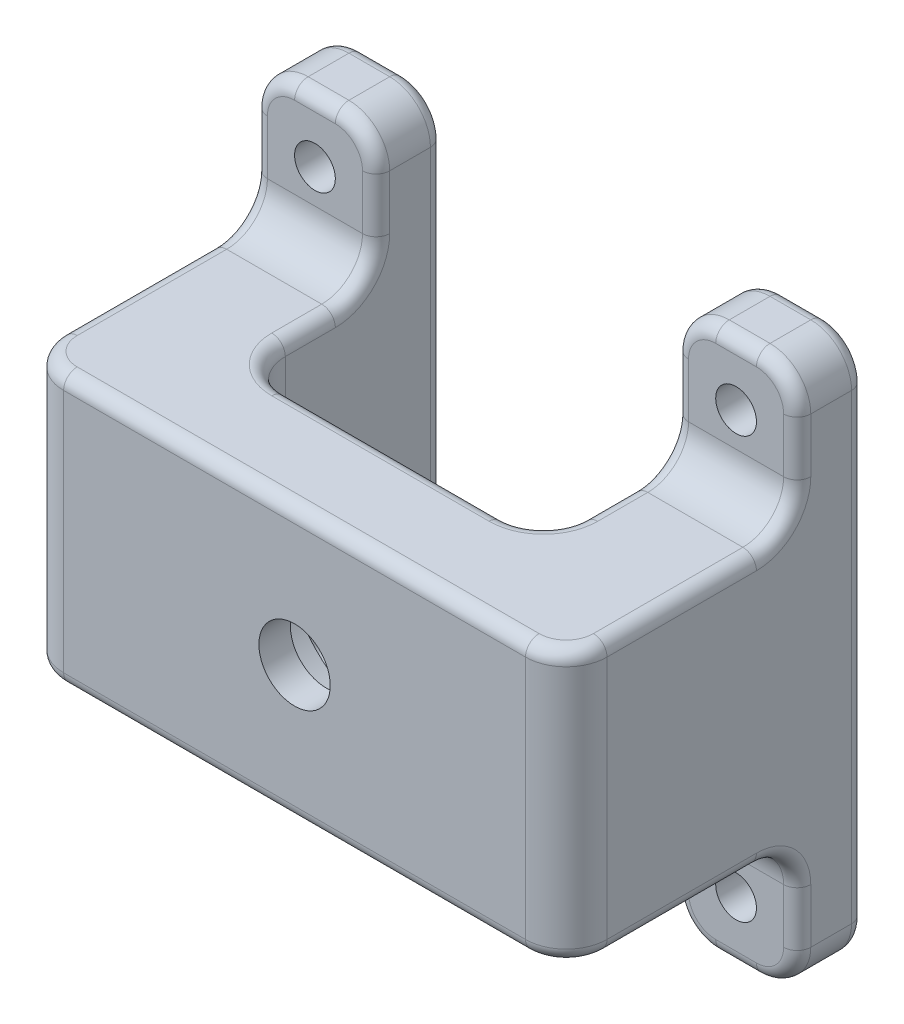
SolidWorks part; units mm, degrees
ref_plane "Front Plane" through (0, 0, 0) normal (0, 0, 1) x (1, 0, 0)
ref_plane "Top Plane" through (0, 0, 0) normal (0, 1, 0) x (1, 0, 0)
ref_plane "Right Plane" through (0, 0, 0) normal (1, 0, 0) x (0, 0, -1)
sketch "Sketch1" plane through (0, 0, 0) normal (0, 0, 1) x (1, 0, 0)
  line L1 (-20, 20) -> (20, 20)
  line L2 (-20, 20) -> (-20, -20)
  line L3 (-20, -20) -> (20, -20)
  line L4 (20, 20) -> (20, -20)
  line L5 (-20, 20) -> (20, -20) construction
  line L6 (-20, -20) -> (20, 20) construction
  point P0 (0, 0)
  dimension "D1" = 40
extrude "Boss-Extrude1" add sketch "Sketch1" along normal blind 22 contours L2 L3 L4 L1
sketch "Sketch2" plane through (0, -20, 0) normal (0, -1, 0) x (1, 0, 0)
  line L0 (-20, 0) -> (20, 0) construction
  line L1 (-11, 0) -> (11, 0)
  line L2 (-11, 0) -> (-11, 14.682)
  line L3 (-11, 14.682) -> (11, 14.682)
  line L4 (11, 0) -> (11, 14.682)
  point P6 (0, 14.682)
  dimension "D1" = 22
  dimension "D2" = 14.682
extrude "Cut-Extrude1" cut sketch "Sketch2" against normal through all
sketch "Sketch3" plane through (0, 0, 14.682) normal (0, 0, -1) x (-1, 0, 0)
  circle A0 centre (0, 0) radius 8
  dimension "D1" = 16
extrude "Cut-Extrude2" cut sketch "Sketch3" against normal blind 5
sketch "Sketch4" plane through (0, 0, 19.682) normal (0, 0, -1) x (-1, 0, 0)
  circle A0 centre (0, 0) radius 2.625
  dimension "D1" = 5.25
extrude "Cut-Extrude3" cut sketch "Sketch4" against normal through all
sketch "Sketch7" plane through (0, 0, 22) normal (0, 0, 1) x (1, 0, 0)
  line L1 (-15.5, -15.5) -> (15.5, -15.5) construction
  line L2 (-15.5, -15.5) -> (-15.5, 15.5) construction
  line L3 (-15.5, 15.5) -> (15.5, 15.5) construction
  line L4 (15.5, -15.5) -> (15.5, 15.5) construction
  line L5 (-15.5, -15.5) -> (15.5, 15.5) construction
  line L6 (-15.5, 15.5) -> (15.5, -15.5) construction
  circle A4 centre (-15.5, 15.5) radius 1.5
  circle A5 centre (15.5, 15.5) radius 1.5
  circle A6 centre (15.5, -15.5) radius 1.5
  circle A7 centre (-15.5, -15.5) radius 1.5
  point P0 (0, 0)
  dimension "D1" = 31
  dimension "D4" = 3
  dimension "D2" = 2
  dimension "D3" = 2
extrude "Cut-Extrude6" cut sketch "Sketch7" against normal through all
sketch "Sketch6" plane through (0, 0, 22) normal (0, 0, 1) x (1, 0, 0)
  line L0 (20, 20) -> (20, -20) construction
  line L5 (-20, -20) -> (20, -20)
  line L7 (-20, -20) -> (-20, -10)
  line L8 (-20, -10) -> (20, -10)
  line L17 (20, -20) -> (20, -10)
  line L19 (-20, 20) -> (20, 20)
  line L20 (-20, 20) -> (-20, 10)
  line L21 (-20, 10) -> (20, 10)
  line L22 (20, 20) -> (20, 10)
  dimension "D1" = 10
extrude "Cut-Extrude4" cut sketch "Sketch6" against normal offset from surface (17 mm away) 5 up to face at (17, -15.5, 0)
fillet "Fillet1" radius 3 16 edges at (-20, 0, 22) (20, 0, 22) (-20, 20, 2.5) (11, 20, 2.5) (-11, 20, 2.5) (20, 20, 2.5) (20, -20, 2.5) (11, -20, 2.5) (-20, -20, 2.5) (-11, -20, 2.5) (11, 0, 14.682) (-11, 0, 14.682) (-15.5, 10, 5) (15.5, 10, 5) (15.5, -10, 5) (-15.5, -10, 5)
fillet "Fillet2" radius 1 64 edges at (-11, -15, 5) (-11.8787, -19.1213, 5) (-15.5, -20, 5) (-19.1213, -19.1213, 5) (-11, 0, 0) (-11.8787, 19.1213, 0) (-15.5, 20, 0) (-19.1213, 19.1213, 0) (-11.8787, -19.1213, 0) (-15.5, -20, 0) (-19.1213, -19.1213, 0) (-11, 15, 5) (-11.8787, 19.1213, 5) (-15.5, 20, 5) (-19.1213, 19.1213, 5) (11, -15, 5) (11.8787, -19.1213, 5) (15.5, -20, 5) (19.1213, -19.1213, 5) (11, 15, 5) (11.8787, 19.1213, 5) (15.5, 20, 5) (19.1213, 19.1213, 5) (11, 0, 0) (11.8787, 19.1213, 0) (15.5, 20, 0) (19.1213, 19.1213, 0) (11.8787, -19.1213, 0) (15.5, -20, 0) (19.1213, -19.1213, 0) (-20, 10, 13.5) (-20, -10, 13.5) (-20, -15, 5) (-20, 0, 0) (-20, 15, 5) (20, -15, 5) (20, -10, 13.5) (20, 10, 13.5) (20, 15, 5) (20, 0, 0) (-11, 10, 9.841) (0, 10, 14.682) (11, 10, 9.841) (11, -10, 9.841) (0, -10, 14.682) (-11, -10, 9.841) (0, 10, 22) (0, -10, 22) (-10.1213, 10, 13.8033) (10.1213, 10, 13.8033) (10.1213, -10, 13.8033) (-10.1213, -10, 13.8033) (-19.1213, 10, 21.1213) (19.1213, 10, 21.1213) (19.1213, -10, 21.1213) (-19.1213, -10, 21.1213) (-11, 10.8787, 5.8787) (11, 10.8787, 5.8787) (11, -10.8787, 5.8787) (-11, -10.8787, 5.8787) (-20, -10.8787, 5.8787) (-20, 10.8787, 5.8787) (20, 10.8787, 5.8787) (20, -10.8787, 5.8787)
